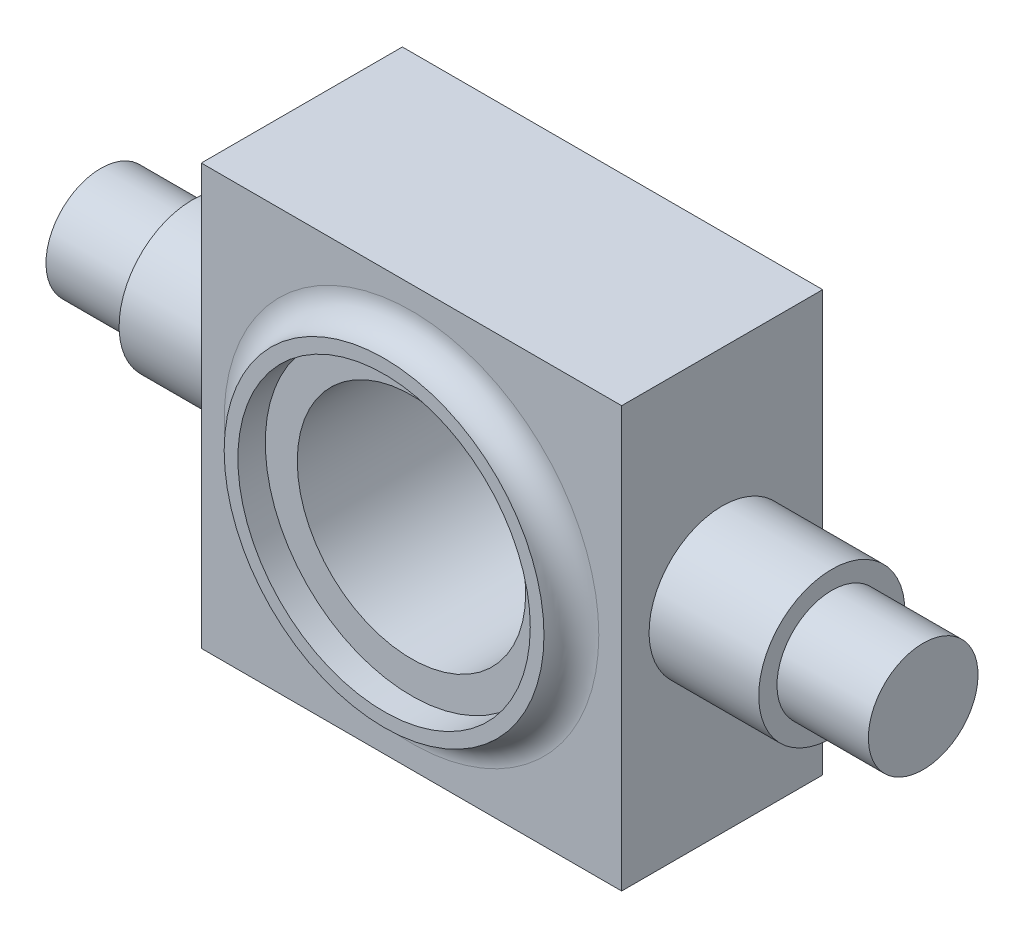
SolidWorks part; units mm, degrees
ref_plane "Front Plane" through (0, 0, 0) normal (0, 0, 1) x (1, 0, 0)
ref_plane "Top Plane" through (0, 0, 0) normal (0, 1, 0) x (1, 0, 0)
ref_plane "Right Plane" through (0, 0, 0) normal (1, 0, 0) x (0, 0, -1)
sketch "Sketch1" plane through (0, 0, 0) normal (0, 0, 1) x (1, 0, 0)
  line L1 (-23, 23) -> (23, 23)
  line L2 (-23, 23) -> (-23, -23)
  line L3 (-23, -23) -> (23, -23)
  line L4 (23, 23) -> (23, -23)
  line L5 (-23, 23) -> (23, -23) construction
  line L6 (-23, -23) -> (23, 23) construction
  point P0 (0, 0)
  dimension "D1" = 46
  dimension "D2" = 46
extrude "Boss-Extrude3" add sketch "Sketch1" along normal mid plane 22
sketch "Sketch3" plane through (0, 0, 11) normal (0, 0, 1) x (1, 0, 0)
  circle A0 centre (0, 0) radius 17.5
  circle A1 centre (0, 0) radius 16
  dimension "D1" = 35
  dimension "D2" = 32
extrude "Boss-Extrude5" add sketch "Sketch3" along normal blind 3
sketch "Sketch6" plane through (0, 0, 11) normal (0, 0, 1) x (1, 0, 0)
  circle A0 centre (0, 0) radius 12.5
  dimension "D1" = 25
extrude "Cut-Extrude2" cut sketch "Sketch6" against normal through all
mirror "Mirror1" about plane through (0, 0, 0) normal (0, 0, 1) of "Boss-Extrude5"
fillet "Fillet1" radius 3 2 edges at (17.5, 0, -11) (17.5, 0, 11)
ref_plane "Plane1" through (0, 0, 0) normal (0, 0, 1) x (1, 0, 0)
sketch "Sketch9" plane through (0, 0, 0) normal (0, 0, 1) x (1, 0, 0)
  line L0 (-60.226, 0) -> (64.7519, 0) construction
  line L1 (0, 45.9123) -> (0, -46.7652) construction
  line L2 (-23, 0) -> (-23, 8)
  line L3 (-23, 23) -> (-23, -23) construction
  line L4 (-23, 8) -> (-35, 8)
  line L5 (-35, 8) -> (-35, 6)
  line L6 (-35, 6) -> (-45, 6)
  line L7 (-45, 6) -> (-45, 0)
  line L8 (-23, 0) -> (-45, 0)
  dimension "D1" = 8
  dimension "D2" = 12
  dimension "D3" = 2
  dimension "D4" = 10
  dimension "D5" = 6
revolve "Revolve1" add sketch "Sketch9" angle 360 about L8
cosmetic thread "Cosmetic Thread1" parameters "D2"=10.344
mirror "Mirror2" about plane through (0, 0, 0) normal (1, 0, 0) of "Revolve1"
